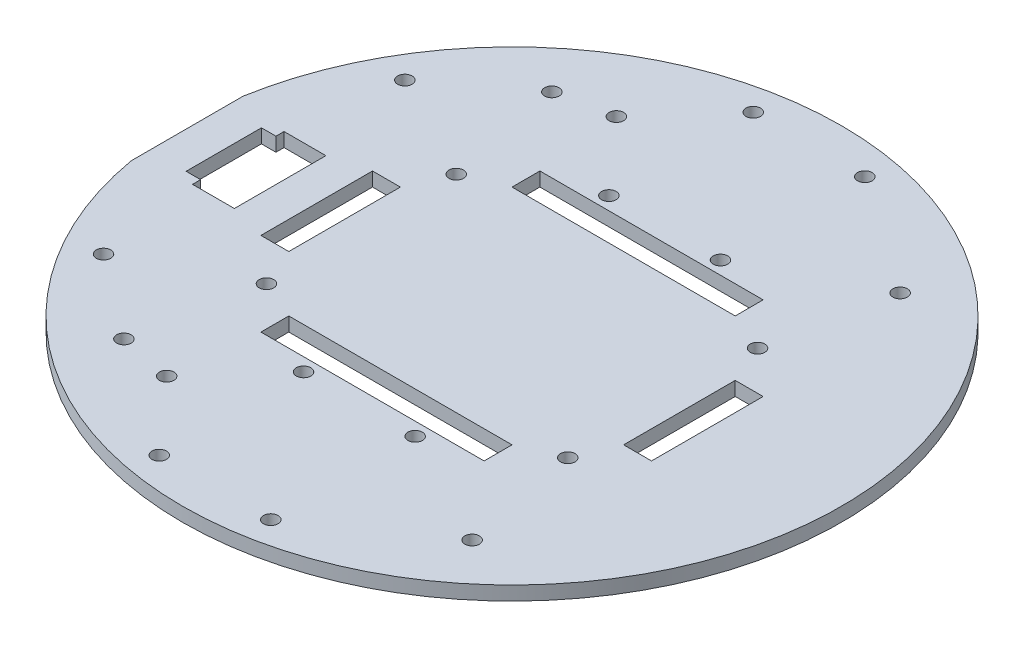
SolidWorks part; units mm, degrees
material "Acrylic (Medium-high impact)"
ref_plane "Front Plane" through (0, 0, 0) normal (0, 0, 1) x (1, 0, 0)
ref_plane "Top Plane" through (0, 0, 0) normal (0, 1, 0) x (1, 0, 0)
ref_plane "Right Plane" through (0, 0, 0) normal (1, 0, 0) x (0, 0, -1)
sketch "Sketch1" plane through (0, 0, 0) normal (0, 1, 0) x (1, 0, 0)
  line L0 (-73.9169, 12.7) -> (-73.9169, -12.7)
  line L1 (-73.9169, 12.7) -> (-73.9169, -12.7) construction
  line L2 (-34.29, 21.59) -> (34.29, 21.59) construction
  line L3 (34.29, 21.59) -> (34.29, -21.59) construction
  line L4 (34.29, -21.59) -> (-34.29, -21.59) construction
  line L5 (-34.29, -21.59) -> (-34.29, 21.59) construction
  line L6 (0, 21.59) -> (0, 75) construction
  line L7 (34.29, 0) -> (75, 0) construction
  line L8 (0, -25.4) -> (0, -21.59) construction
  line L9 (-34.29, 0) -> (-38.1, 0) construction
  line L10 (-25.4, 31.75) -> (25.4, 31.75)
  line L11 (-25.4, 31.75) -> (-25.4, 25.4)
  line L12 (-25.4, 25.4) -> (25.4, 25.4)
  line L13 (25.4, 31.75) -> (25.4, 25.4)
  line L14 (38.1, 12.7) -> (44.45, 12.7)
  line L15 (38.1, 12.7) -> (38.1, -12.7)
  line L16 (38.1, -12.7) -> (44.45, -12.7)
  line L17 (44.45, 12.7) -> (44.45, -12.7)
  line L18 (25.4, -25.4) -> (-25.4, -25.4)
  line L19 (25.4, -25.4) -> (25.4, -31.75)
  line L20 (25.4, -31.75) -> (-25.4, -31.75)
  line L21 (-25.4, -25.4) -> (-25.4, -31.75)
  line L22 (-44.45, -12.7) -> (-38.1, -12.7)
  line L23 (-44.45, -12.7) -> (-44.45, 12.7)
  line L24 (-44.45, 12.7) -> (-38.1, 12.7)
  line L25 (-38.1, -12.7) -> (-38.1, 12.7)
  line L26 (38.1, 12.7) -> (34.29, 12.7) construction
  line L27 (25.4, 25.4) -> (25.4, 21.59) construction
  line L28 (-24.25, -37.9184) -> (24.25, -37.9184) construction
  line L29 (24.25, -37.9184) -> (24.25, -64.4184) construction
  line L30 (-12.7, -37.9184) -> (-12.7, -34.7434) construction
  line L31 (24.25, -64.4184) -> (-24.25, -64.4184) construction
  line L32 (-24.25, -64.4184) -> (-24.25, -37.9184) construction
  line L33 (-24.25, -64.4184) -> (-26.4232, -70.1913) construction
  line L34 (24.25, -64.4184) -> (26.4232, -70.1913) construction
  line L35 (-24.25, -37.9184) -> (-24.25, -31.75) construction
  line L36 (0, -37.9184) -> (0, -64.4184) construction
  line L37 (-52.77, 0) -> (-44.45, 0) construction
  line L38 (-27.425, -51.1684) -> (-24.25, -51.1684) construction
  line L39 (-12.7, -67.5934) -> (-12.7, -64.4184) construction
  line L40 (-65.597, 8.5725) -> (-62.295, 8.5725)
  line L41 (-65.597, 8.5725) -> (-65.597, -8.5725)
  line L42 (-65.597, -8.5725) -> (-62.295, -8.5725)
  line L43 (-52.77, 8.5725) -> (-52.77, -8.5725)
  line L44 (-62.295, 8.5725) -> (-62.295, 10.414)
  line L45 (-62.295, 10.414) -> (-52.77, 10.414)
  line L46 (-52.77, 10.414) -> (-52.77, 8.5725)
  line L47 (-62.295, -8.5725) -> (-62.295, -10.414)
  line L48 (-62.295, -10.414) -> (-52.77, -10.414)
  line L49 (-52.77, -10.414) -> (-52.77, -8.5725)
  line L50 (-65.597, 0) -> (-73.9169, 0) construction
  line L51 (55.1757, 50.8) -> (55.1757, -50.8) construction
  arc A0 (-73.9169, -12.7) -> (-73.9169, 12.7) centre (0, 0) ccw
  arc A1 (55.356, -50.6035) -> (55.356, 50.6035) centre (0, 0) ccw construction
  circle A2 centre (-34.29, 21.59) radius 1.651
  circle A3 centre (34.29, 21.59) radius 1.651
  circle A4 centre (-34.29, -21.59) radius 1.651
  circle A5 centre (34.29, -21.59) radius 1.651
  circle A6 centre (-39.6269, 48.6985) radius 1.651 construction
  circle A7 centre (39.6269, -48.6985) radius 1.651
  circle A8 centre (-39.6269, -48.6985) radius 1.651
  circle A9 centre (-58.6769, -34.29) radius 1.651
  circle A10 centre (-58.6769, 34.29) radius 1.651
  circle A11 centre (-39.6269, 48.6985) radius 1.651
  circle A12 centre (39.6269, 48.6985) radius 1.651
  circle A13 centre (39.6269, -48.6985) radius 1.651 construction
  circle A14 centre (12.7, -67.5934) radius 1.651
  circle A15 centre (12.7, -34.7434) radius 1.651
  circle A16 centre (12.7, 34.7434) radius 1.651
  circle A17 centre (12.7, 67.5934) radius 1.651
  circle A22 centre (-27.425, -51.1684) radius 1.651
  circle A23 centre (-12.7, -34.7434) radius 1.651
  circle A24 centre (-12.7, -67.5934) radius 1.651
  circle A25 centre (-12.7, 67.5934) radius 1.651
  circle A26 centre (-27.425, 51.1684) radius 1.651
  circle A27 centre (-12.7, 34.7434) radius 1.651
  dimension "D11" = 3.302
  dimension "D1" = 68.58
  dimension "D2" = 43.18
  dimension "D3" = 3.81
  dimension "D4" = 6.35
  dimension "D5" = 50.8
  dimension "D6" = 25.4
  dimension "D7" = 48.5
  dimension "D8" = 26.5
  dimension "D9" = 12.7
  dimension "D10" = 3.175
  dimension "D12" = 17.145
  dimension "D14" = 101.6
  dimension "D15" = 3.302
  dimension "D16" = 20.828
  dimension "D17" = 9.525
extrude "Boss-Extrude1" add sketch "Sketch1" along normal blind 3.175
